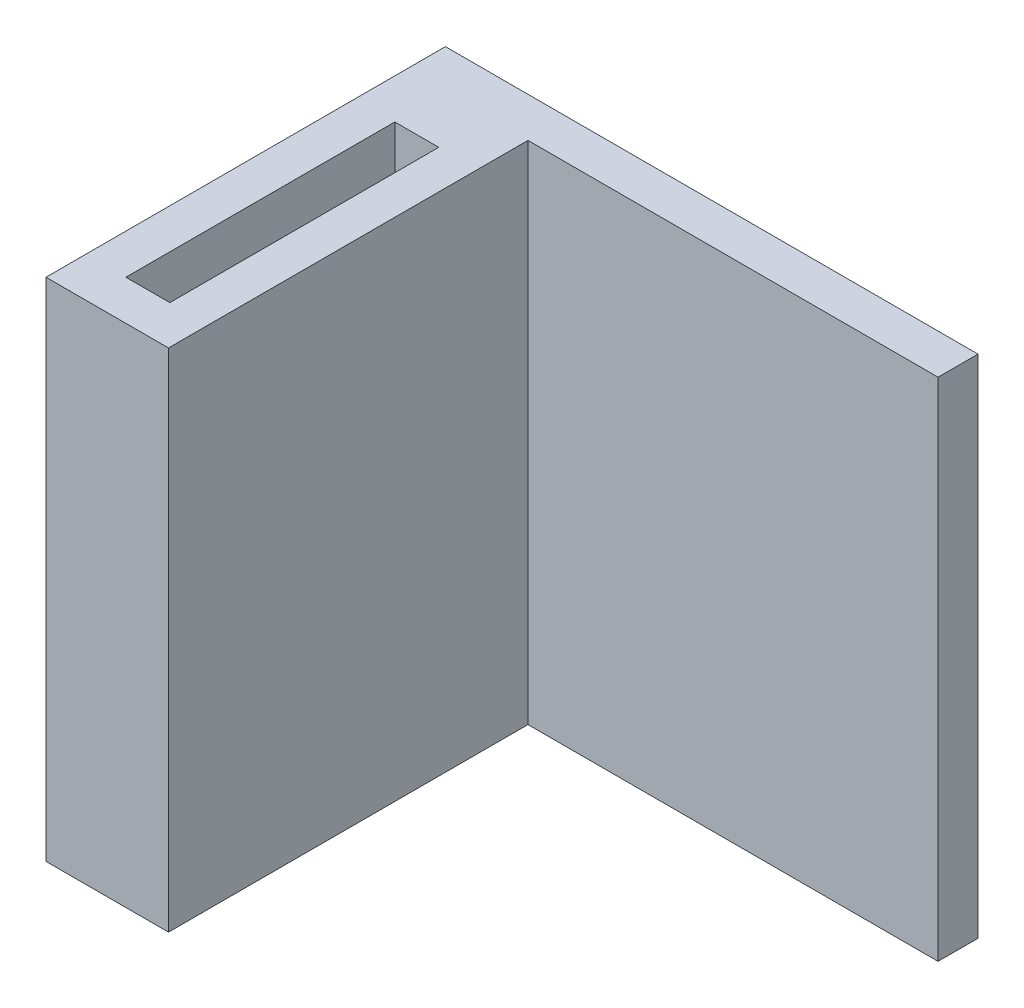
SolidWorks part; units mm, degrees
ref_plane "Front Plane" through (0, 0, 0) normal (0, 0, 1) x (1, 0, 0)
ref_plane "Top Plane" through (0, 0, 0) normal (0, 1, 0) x (1, 0, 0)
ref_plane "Right Plane" through (0, 0, 0) normal (1, 0, 0) x (0, 0, -1)
sketch "Sketch1" plane through (0, 0, 0) normal (0, 1, 0) x (1, 0, 0)
  line L0 (0, 0) -> (0, 15)
  line L1 (0, 15) -> (20, 15)
  line L2 (20, 15) -> (20, 13.5)
  line L3 (20, 13.5) -> (4.6, 13.5)
  line L4 (4.6, 13.5) -> (4.6, 0)
  line L5 (4.6, 0) -> (0, 0)
  line L7 (1.5, 1.5) -> (3.15, 1.5)
  line L8 (1.5, 1.5) -> (1.5, 11.6)
  line L9 (1.5, 11.6) -> (3.15, 11.6)
  line L10 (3.15, 1.5) -> (3.15, 11.6)
  dimension "D1" = 20
  dimension "D2" = 15
  dimension "D3" = 1.5
  dimension "D4" = 4.6
  dimension "D5" = 1.65
  dimension "D6" = 1.5
  dimension "D7" = 10.1
  dimension "D8" = 1.5
  dimension "D9" = 1.45
extrude "Boss-Extrude1" add sketch "Sketch1" along normal blind 4.5 contours L5 L0 L1 L2 L3 L4
extrude "Boss-Extrude2" add sketch "Sketch1<3>" along normal blind 19
sketch "Sketch1<3>" plane through (0, 0, 0) normal (0, 1, 0) x (1, 0, 0) same geometry as "Sketch1"
